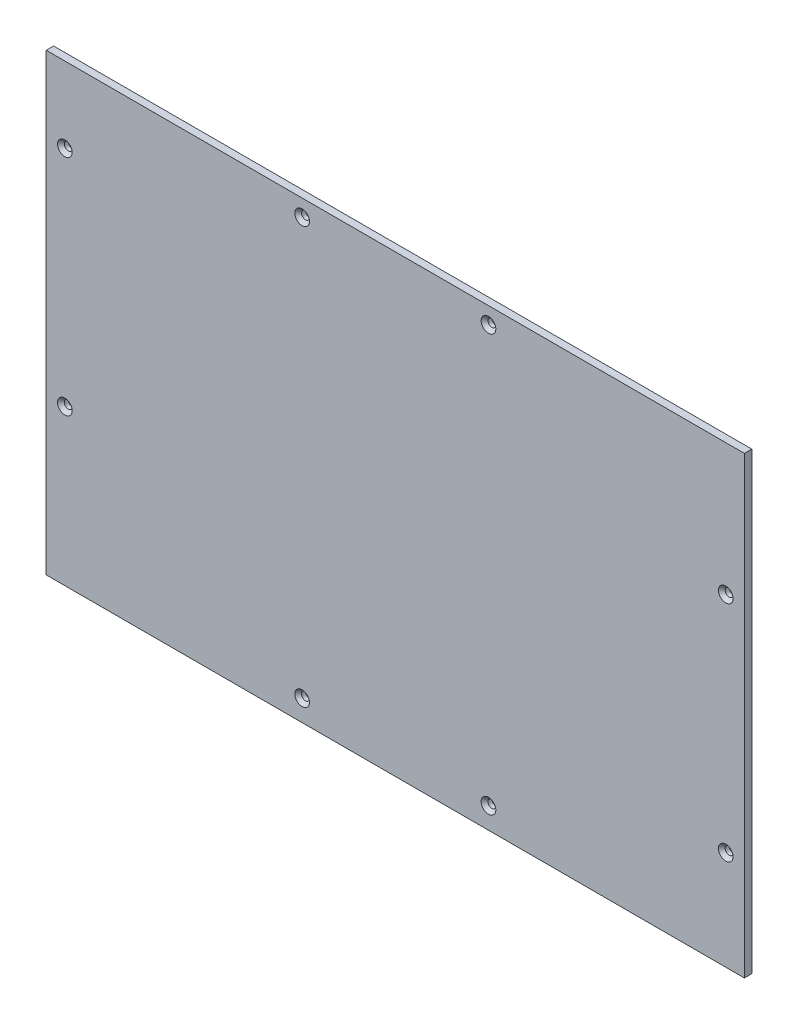
SolidWorks part; units mm, degrees
material "ABS"
ref_plane "X-Y Datum" through (0, 0, 0) normal (0, 0, 1) x (1, 0, 0)
ref_plane "X-Z Datum" through (0, 0, 0) normal (0, 1, 0) x (1, 0, 0)
ref_plane "Y-Z Datum" through (0, 0, 0) normal (1, 0, 0) x (0, 0, -1)
sketch "Sketch1" plane through (0, 0, 0) normal (0, 0, 1) x (1, 0, 0)
  line L0 (-149.85, 97.5219) -> (-149.85, -97.5219)
  line L1 (-149.85, 97.5219) -> (149.85, 97.5219)
  line L2 (-149.85, 97.5219) -> (-149.85, -97.5219)
  line L3 (-149.85, -97.5219) -> (149.85, -97.5219)
  line L4 (149.85, 97.5219) -> (149.85, -97.5219)
  line L5 (-149.85, 97.5219) -> (149.85, -97.5219) construction
  line L6 (-149.85, -97.5219) -> (149.85, 97.5219) construction
  line L7 (-149.85, -97.5219) -> (149.85, -97.5219)
  line L8 (149.85, 97.5219) -> (149.85, -97.5219)
  line L9 (-149.85, 97.5219) -> (149.85, 97.5219)
  circle A0 centre (-139.075, -86.7469) radius 10.775
  circle A1 centre (-115.075, -86.7469) radius 10.775 construction
  circle A2 centre (-127.075, -63.7469) radius 10.775
  point P0 (0, 0)
  dimension "D1" = 21.55
  dimension "D2" = 24
  dimension "D3" = 23
  dimension "D4" = 12
  dimension "D5" = 195.0437
  dimension "D6" = 299.7
  dimension "D7" = 0
extrude "Boss-Extrude1" add sketch "Sketch1" along normal blind 3.175 contours A0 L3 L4 L1 L2 A2 | A2 | A0 | A0 L2 L3 | L9 L0 L7 L8 L1 L4 L3 L2 region at (1.7461, 0.9924, 0) region at (-147.4432, -95.1151, 0) region at (-139.075, -86.7469, 0) region at (-127.075, -63.7469, 0)
sketch "Sketch2" plane through (0, 0, 3.175) normal (0, 0, 1) x (1, 0, 0)
  point P0 (40, -88.4276)
  point P1 (-40, -88.4276)
  point P3 (-141.85, -30.9219)
  point P5 (-141.85, 65.0781)
  point P7 (-40, 90.3781)
  point P9 (40, 90.3781)
  point P11 (141.85, 41.0781)
  point P13 (141.85, -54.9219)
hole_wizard "CSK for M3 Flat Head Machine Screw1" positions "Sketch5" profile "Sketch4" countersink size "M3" standard "ANSI Metric" end condition through all
sketch "Sketch5" plane through (0, 0, 3.175) normal (0, 0, 1) x (1, 0, 0)
  point P0 (-40, 90.3781)
  point P3 (40, 90.3781)
  point P6 (141.85, 41.0781)
  point P9 (141.85, -54.9219)
  point P12 (40, -88.4276)
  point P15 (-40, -88.4276)
  point P18 (-141.85, -30.9219)
  point P21 (-141.85, 65.0781)
sketch "Sketch4" plane through (-40, 90.3781, 3.175) normal (1, 0, 0) x (0, -1, 0)
  line L0 (0, 0) -> (0, 3.175)
  line L1 (0, 3.175) -> (1.7, 3.175)
  line L2 (1.7, 3.175) -> (1.7, 1.45)
  line L3 (1.7, 1.45) -> (3.15, 0)
  line L5 (3.15, 0) -> (0, 0)
  line L6 (-1.7, 1.45) -> (-3.15, 0) construction
  line L11 (0, -6.35) -> (0, 107.95) construction
  dimension "Thru Hole Dia." = 3.4
  dimension "Thru Hole Depth" = 3.175
  dimension "Near C'Sink Dia." = 6.3
  dimension "Near C'Sink Angle" = 90
